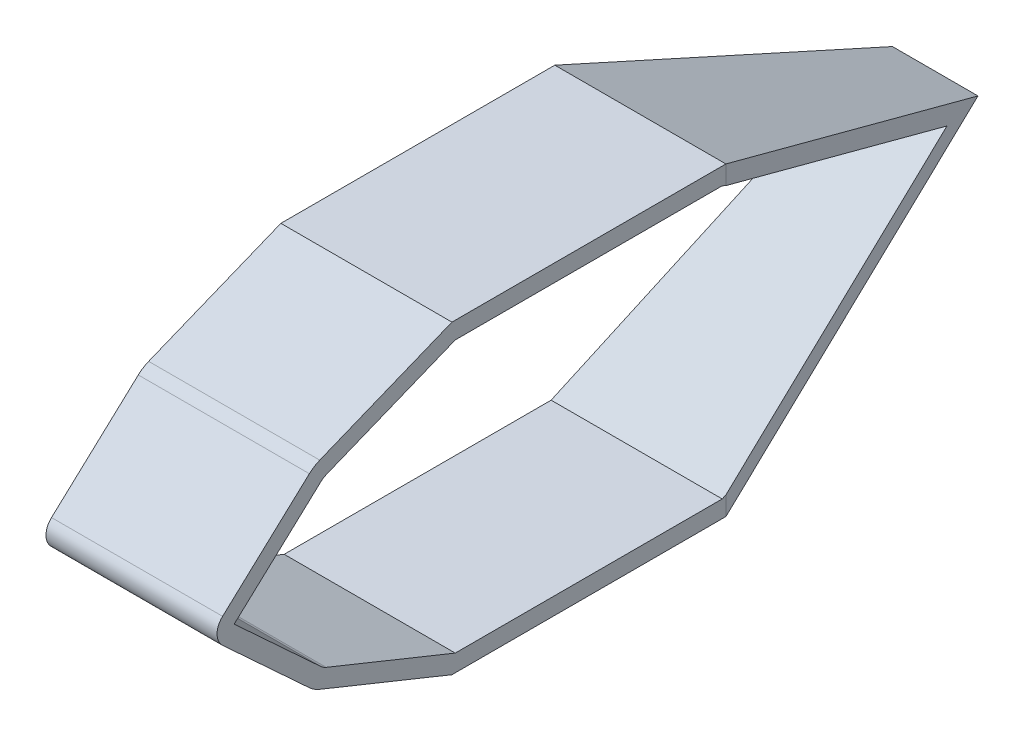
SolidWorks part; units mm, degrees
ref_plane "Front Plane" through (0, 0, 0) normal (1, 0, 0) x (0, 1, 0)
ref_plane "Top Plane" through (0, 0, 0) normal (0, 0, 1) x (0, 1, 0)
ref_plane "Right Plane" through (0, 0, 0) normal (0, 1, 0) x (-1, 0, 0)
sketch "Sketch1" plane through (0, 0, 0) normal (1, 0, 0) x (0, 1, 0)
  line L0 (-1000, 0) -> (49000, 0) construction
  line L1 (0, -1000) -> (0, 49000) construction
  line L2 (-44.6275, -40.0348) -> (-44.6275, 40.0348)
  line L3 (44.6275, -40.0348) -> (44.6275, 40.0348)
  line L4 (-44.6275, 40.0348) -> (-29.0103, 78.6676)
  line L5 (-27.0873, 81.7026) -> (-3.674, 107.0672)
  line L6 (27.0873, 81.7026) -> (3.674, 107.0672)
  line L7 (44.6275, 40.0348) -> (29.0103, 78.6676)
  line L12 (-44.6275, -40.0348) -> (0, -138.7195)
  line L13 (44.6275, -40.0348) -> (0, -138.7195)
  arc A0 (27.0873, 81.7026) -> (29.0103, 78.6676) centre (19.7392, 74.9198) cw
  arc A1 (-29.0103, 78.6676) -> (-27.0873, 81.7026) centre (-19.7392, 74.9198) cw
  arc A2 (-3.674, 107.0672) -> (3.674, 107.0672) centre (0, 103.6759) cw
  point P10 (44.6275, 0)
  point P11 (-44.6275, 0)
  point P20 (28.3259, 80.3607)
  point P23 (-28.3259, 80.3607)
  point P26 (0, 111.0475)
  dimension "D1" = 10
  dimension "D2" = 5
extrude "Boss-Extrude1" add sketch "Sketch1" along normal blind 50
shell "Shell1" thickness 5 removed face at (0, 0, 36.1762) removed face at (50, 0, 36.1762)
sketch "Sketch3" plane through (0, 44.6275, 0) normal (0, 1, 0) x (-1, 0, 0)
  line L0 (-50, -40.0348) -> (-25, -138.7195)
  line L1 (-50, -138.7195) -> (0, -138.7195) construction
  line L2 (-25, -138.7195) -> (-50, -138.7195)
  line L3 (-50, -138.7195) -> (-50, -40.0348)
extrude "Cut-Extrude2" cut sketch "Sketch3" against normal through all
